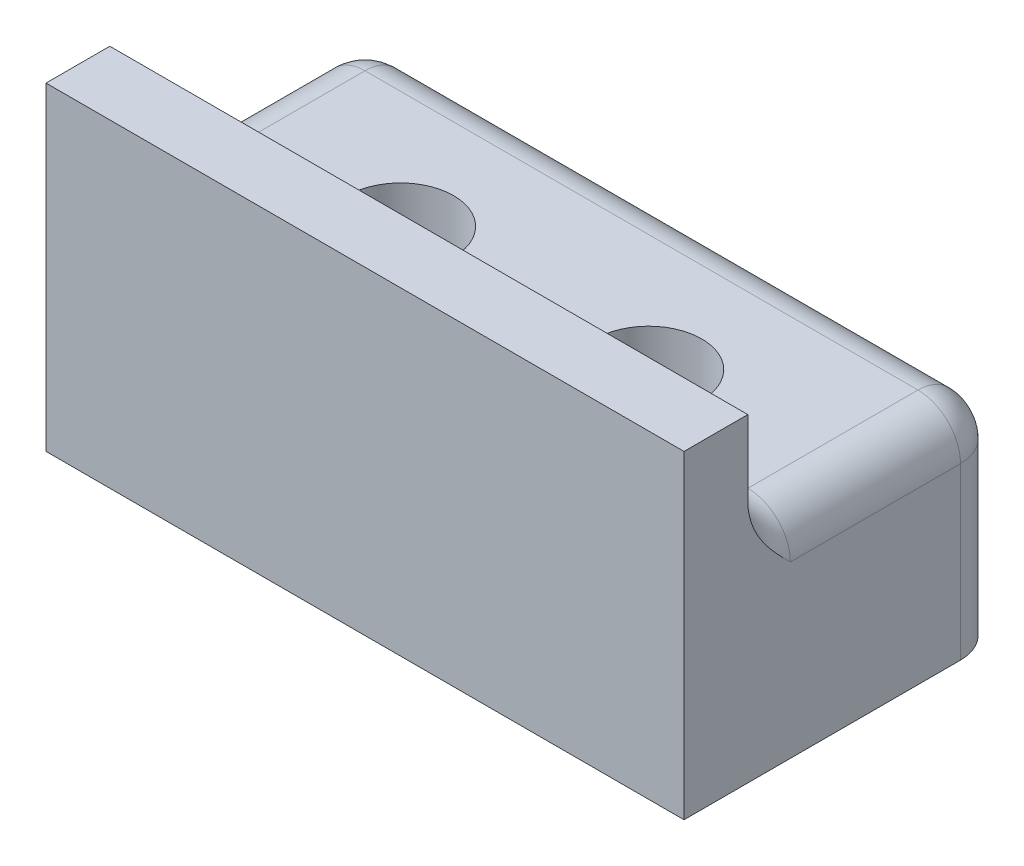
SolidWorks part; units mm, degrees
material "6061-T6 (anodized black)"
ref_plane "Front Plane" through (0, 0, 0) normal (0, 0, 1) x (1, 0, 0)
ref_plane "Top Plane" through (0, 0, 0) normal (0, 1, 0) x (1, 0, 0)
ref_plane "Right Plane" through (0, 0, 0) normal (1, 0, 0) x (0, 0, -1)
sketch "Sketch1" plane through (0, 0, 0) normal (0, 1, 0) x (1, 0, 0)
  line L1 (-19.05, -9.525) -> (19.05, -9.525)
  line L2 (-19.05, -9.525) -> (-19.05, 9.525)
  line L3 (-19.05, 9.525) -> (19.05, 9.525)
  line L4 (19.05, -9.525) -> (19.05, 9.525)
  line L5 (-19.05, -9.525) -> (19.05, 9.525) construction
  line L6 (-19.05, 9.525) -> (19.05, -9.525) construction
  line L7 (7.4083, 9.525) -> (7.4083, -9.525) construction
  line L8 (0, -9.525) -> (0, 9.525) construction
  line L9 (10.5833, 0) -> (19.05, 0) construction
  line L10 (4.2333, 0) -> (-4.2333, 0) construction
  circle A0 centre (7.4083, 0) radius 3.175
  circle A1 centre (-7.4083, 0) radius 3.175
  point P0 (0, 0)
  point P11 (0, 0)
  dimension "D4" = 6.35
  dimension "D1" = 19.05
  dimension "D2" = 38.1
extrude "Boss-Extrude1" add sketch "Sketch1" along normal blind 12.7
sketch "Sketch3" plane through (0, 12.7, 0) normal (0, 1, 0) x (1, 0, 0)
  line L0 (-19.05, 9.525) -> (-19.05, -9.525) construction
  line L1 (-19.05, -5.715) -> (19.05, -5.715)
  line L2 (-19.05, -5.715) -> (-19.05, -9.525)
  line L3 (-19.05, -9.525) -> (19.05, -9.525)
  line L4 (19.05, -5.715) -> (19.05, -9.525)
  line L5 (-19.05, -5.715) -> (19.05, -9.525) construction
  line L6 (-19.05, -9.525) -> (19.05, -5.715) construction
  point P4 (0, -7.62)
  dimension "D1" = 3.81
extrude "Boss-Extrude2" add sketch "Sketch3" along normal blind 6.35
fillet "Fillet1" radius 2.54 5 edges at (19.05, 6.35, -9.525) (-19.05, 6.35, -9.525) (-19.05, 12.7, -1.905) (19.05, 12.7, -1.905) (0, 12.7, -9.525)
fillet "Fillet2" radius 2.54 3 edges at (18.3061, 11.9561, 5.715) (-18.3061, 11.9561, 5.715) (0, 12.7, 5.715)
